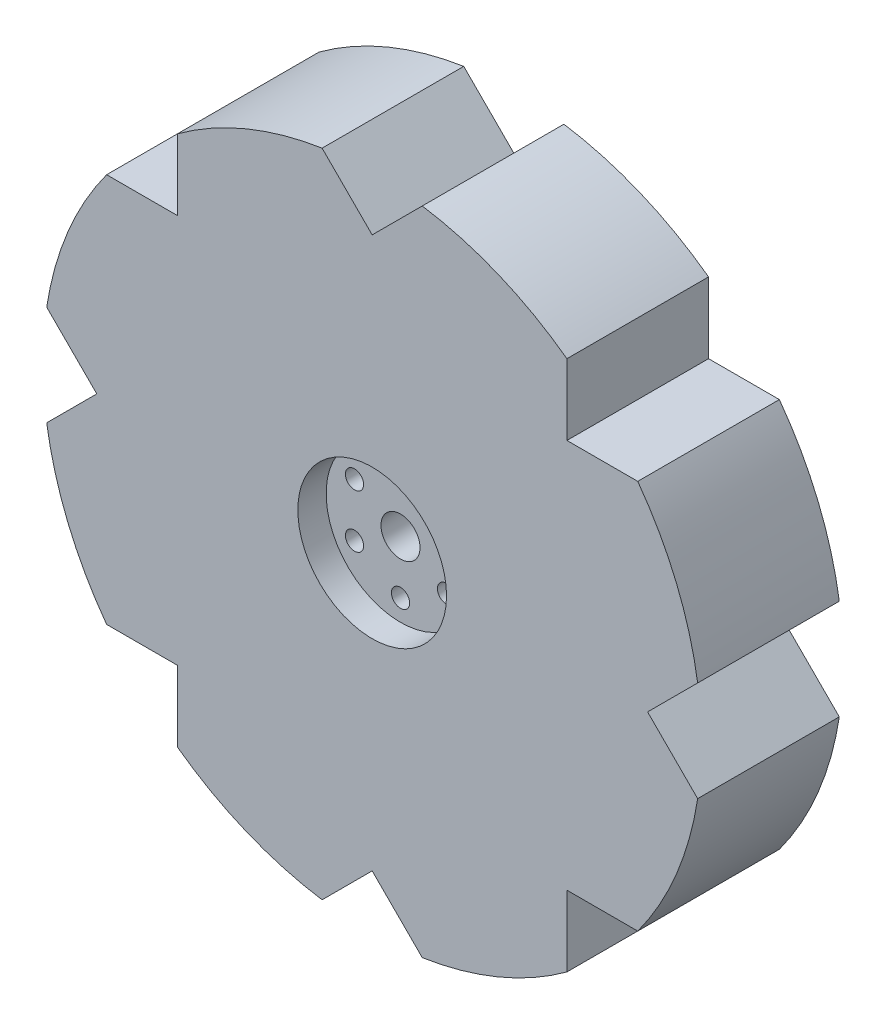
SolidWorks part; units mm, degrees
material "PE High Density Film"
ref_plane "Front Plane" through (0, 0, 0) normal (0, 0, 1) x (1, 0, 0)
ref_plane "Top Plane" through (0, 0, 0) normal (0, 1, 0) x (1, 0, 0)
ref_plane "Right Plane" through (0, 0, 0) normal (1, 0, 0) x (0, 0, -1)
sketch "Sketch1" plane through (0, 0, 0) normal (0, 0, 1) x (1, 0, 0)
  line L0 (0, 0) -> (0, 59.055) construction
  line L1 (-8.9803, 58.3682) -> (0, 49.388)
  line L2 (0, 49.388) -> (8.9803, 58.3682)
  line L3 (34.9226, 47.6226) -> (34.9226, 34.9226)
  line L4 (34.9226, 34.9226) -> (47.6226, 34.9226)
  line L5 (58.3682, 8.9803) -> (49.388, 0)
  line L6 (49.388, 0) -> (58.3682, -8.9803)
  line L7 (47.6226, -34.9226) -> (34.9226, -34.9226)
  line L8 (34.9226, -34.9226) -> (34.9226, -47.6226)
  line L9 (8.9803, -58.3682) -> (0, -49.388)
  line L10 (0, -49.388) -> (-8.9803, -58.3682)
  line L11 (-34.9226, -47.6226) -> (-34.9226, -34.9226)
  line L12 (-34.9226, -34.9226) -> (-47.6226, -34.9226)
  line L13 (-58.3682, -8.9803) -> (-49.388, 0)
  line L14 (-49.388, 0) -> (-58.3682, 8.9803)
  line L15 (-47.6226, 34.9226) -> (-34.9226, 34.9226)
  line L16 (-34.9226, 34.9226) -> (-34.9226, 47.6226)
  arc A0 (-58.3682, -8.9803) -> (-47.6226, -34.9226) centre (0, 0) ccw
  arc A1 (-47.6226, 34.9226) -> (-58.3682, 8.9803) centre (0, 0) ccw
  arc A2 (-34.9226, -47.6226) -> (-8.9803, -58.3682) centre (0, 0) ccw
  arc A3 (8.9803, -58.3682) -> (34.9226, -47.6226) centre (0, 0) ccw
  arc A4 (47.6226, -34.9226) -> (58.3682, -8.9803) centre (0, 0) ccw
  arc A5 (58.3682, 8.9803) -> (47.6226, 34.9226) centre (0, 0) ccw
  arc A6 (34.9226, 47.6226) -> (8.9803, 58.3682) centre (0, 0) ccw
  arc A7 (-8.9803, 58.3682) -> (-34.9226, 47.6226) centre (0, 0) ccw
  point P30 (0, 0)
  dimension "D1" = 118.11
  dimension "D2" = 45
  dimension "D3" = 12.7
  dimension "D4" = 8
extrude "Boss-Extrude1" add sketch "Sketch1" along normal blind 25.4
sketch "Sketch2" plane through (0, 0, 25.4) normal (0, 0, 1) x (1, 0, 0)
  circle A0 centre (0, 0) radius 3.5
  dimension "D1" = 7
extrude "Cut-Extrude1" cut sketch "Sketch2" against normal through all contours A0 region at (0, 0, 25.4)
sketch "Sketch3" plane through (0, 0, 25.4) normal (0, 0, 1) x (1, 0, 0)
  circle A0 centre (0, 0) radius 13.335
  dimension "D1" = 26.67
extrude "Cut-Extrude2" cut sketch "Sketch3" against normal blind 5.08
sketch "Sketch4" plane through (0, 0, 0) normal (0, 0, -1) x (-1, 0, 0)
  circle A0 centre (0, 0) radius 22.86
  dimension "D1" = 45.72
extrude "Cut-Extrude3" cut sketch "Sketch4" against normal blind 5.08
sketch "Sketch5" plane through (0, 0, 5.08) normal (0, 0, -1) x (-1, 0, 0)
  line L0 (0, 0) -> (0, 9.525) construction
  circle A0 centre (0, 0) radius 9.525 construction
  circle A1 centre (0, 9.525) radius 1.5875
  circle A2 centre (8.2489, 4.7625) radius 1.5875
  circle A3 centre (8.2489, -4.7625) radius 1.5875
  circle A4 centre (0, -9.525) radius 1.5875
  circle A5 centre (-8.2489, -4.7625) radius 1.5875
  circle A6 centre (-8.2489, 4.7625) radius 1.5875
  point P17 (0, 0)
  dimension "D1" = 19.05
  dimension "D2" = 3.175
  dimension "D3" = 6
hole_wizard "#4 Clearance Hole1" positions "Sketch6" profile "Sketch8" hole size "#4" standard "ANSI Inch" end condition through all
sketch "Sketch6" plane through (0, 0, 5.08) normal (0, 0, -1) x (-1, 0, 0)
  point P0 (0, 9.525)
  point P3 (8.2489, 4.7625)
  point P6 (8.2489, -4.7625)
  point P9 (0, -9.525)
  point P13 (-8.2489, 4.7625)
  point P16 (-8.2489, -4.7625)
sketch "Sketch8" plane through (0, 9.525, 5.08) normal (1, 0, 0) x (0, 1, 0)
  line L0 (0, 0) -> (0, 20.32)
  line L1 (0, 20.32) -> (1.6319, 20.32)
  line L2 (1.6319, 20.32) -> (1.6319, 0)
  line L5 (1.6319, 0) -> (0, 0)
  line L11 (0, -6.35) -> (0, 107.95) construction
  dimension "Thru Hole Dia." = 3.2639
  dimension "Thru Hole Depth" = 20.32
